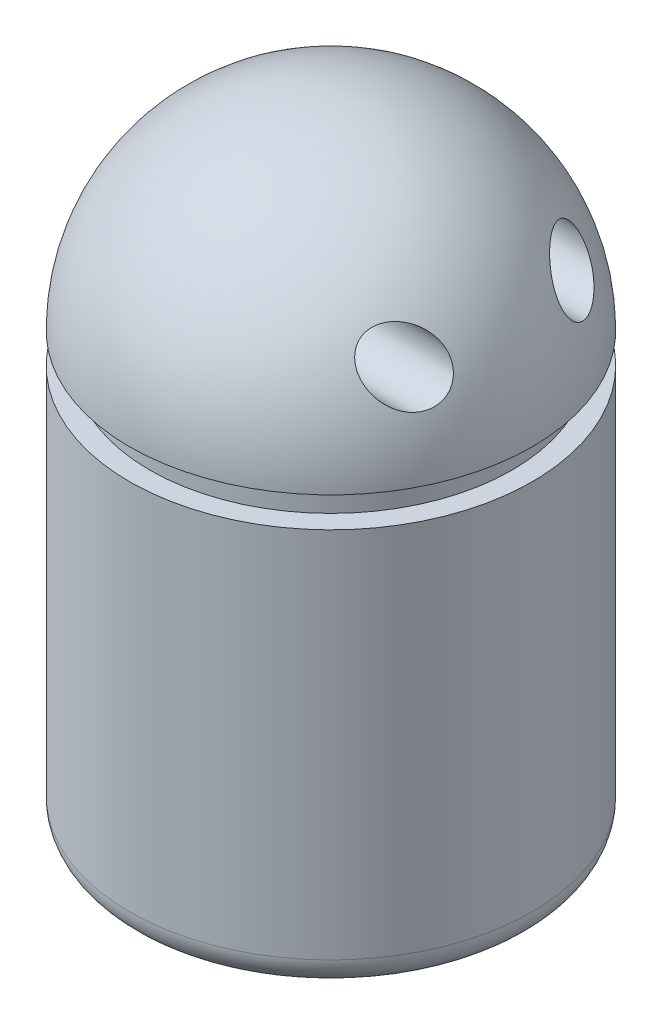
SolidWorks part; units mm, degrees
ref_plane "Alzado" through (0, 0, 0) normal (0, 0, 1) x (1, 0, 0)
ref_plane "Planta" through (0, 0, 0) normal (0, 1, 0) x (1, 0, 0)
ref_plane "Vista lateral" through (0, 0, 0) normal (1, 0, 0) x (0, 0, -1)
sketch "Croquis4" plane through (0, 0, 0) normal (0, 0, 1) x (1, 0, 0)
  line L0 (-20, 25.0872) -> (-20, -17.9128) construction
  line L1 (-20, -17.9128) -> (0, -17.9128) construction
  line L2 (20, -17.9128) -> (20, 22.0839)
  line L3 (0, 45.0872) -> (0, -17.9128)
  line L4 (0, -17.9128) -> (20, -17.9128)
  line L5 (20, 25.0872) -> (18, 25.0872)
  line L6 (18, 25.0872) -> (18, 22.0839)
  line L7 (18, 22.0839) -> (20, 22.0839)
  arc A0 (20, 25.0872) -> (0, 45.0872) centre (0, 25.0872) ccw
  arc A1 (-20, 25.0872) -> (0, 45.0872) centre (0, 25.0872) cw construction
  dimension "D1" = 63
  dimension "D4" = 2
  dimension "D2" = 20
  dimension "D3" = 43
  dimension "D5" = 3.0033
revolve "Revolución4" add sketch "Croquis4" angle 360 about L3
fillet "Redondeo3" radius 3 1 edges at (-20, -17.9128, 0)
sketch "Croquis9" plane through (0, 0, 0) normal (1, 0, 0) x (0, 0, -1)
  line L0 (0, 60.2525) -> (0, -25.4873) construction
  circle A1 centre (8.2616, 33.8856) radius 3
  circle A2 centre (-8.2616, 33.8856) radius 3
extrude "Cortar-Extruir3" cut sketch "Croquis9" along normal blind 18
